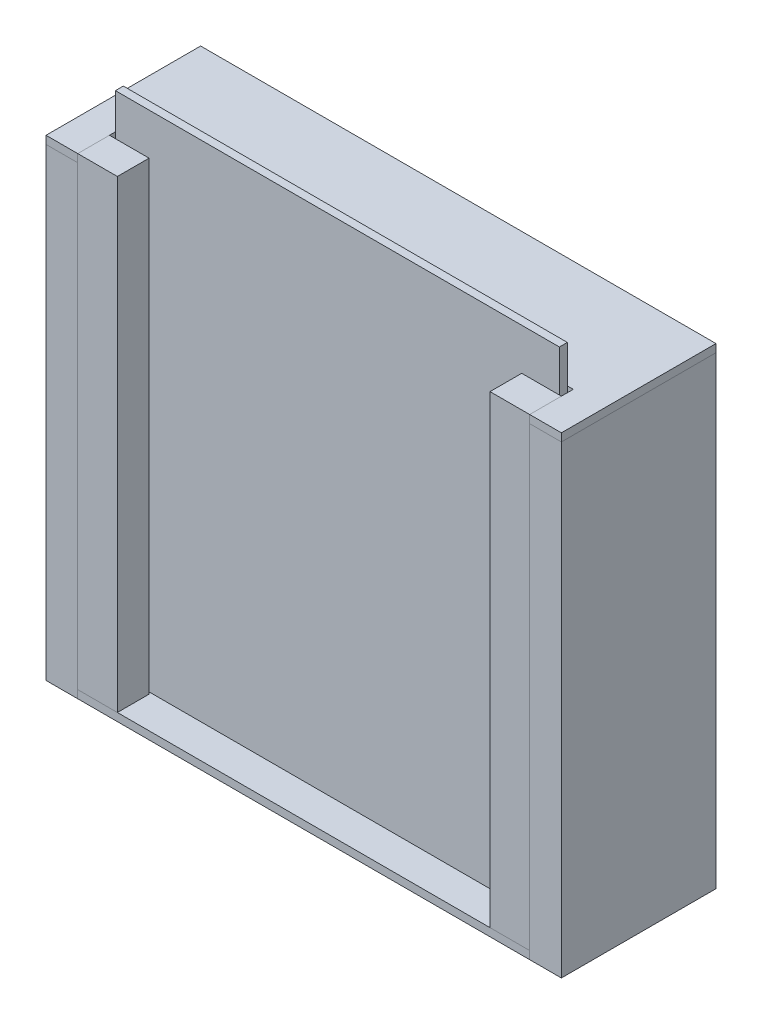
SolidWorks part; units mm, degrees
note: The reader was unsure of these and kept them because the rebuilt part matched: shared geometry of "스케치8<3>".
other "카메라1mm문"
other "카메라4mm 바깥레일2"
other "카메라4mm 바깥레일1"
other "카메라4mm 안쪽레일2"
other "카메라4mm 안쪽레일1"
other "카메라1mm천장"
other "카메라4mm벽2"
other "카메라4mm벽1"
other "바닥 1mm"
other "바닥1mm"
ref_plane "정면" through (0, 0, 0) normal (0, 0, 1) x (1, 0, 0)
ref_plane "윗면" through (0, 0, 0) normal (0, 1, 0) x (1, 0, 0)
ref_plane "우측면" through (0, 0, 0) normal (1, 0, 0) x (0, 0, -1)
sketch "스케치6" plane through (0, 0, 0) normal (0, 0, 1) x (1, 0, 0)
  line L1 (-32.5, 121.5) -> (-28.5, 121.5)
  line L2 (-32.5, 121.5) -> (-32.5, 180.05)
  line L3 (-32.5, 180.05) -> (-28.5, 180.05)
  line L4 (-28.5, 121.5) -> (-28.5, 180.05)
  line L5 (0, 181.05) -> (0, 118.3412) construction
  line L6 (-32.5, 181.05) -> (32.5, 181.05) construction
  line L7 (32.5, 121.5) -> (28.5, 121.5)
  line L8 (28.5, 121.5) -> (28.5, 180.05)
  line L9 (32.5, 180.05) -> (28.5, 180.05)
  line L10 (32.5, 121.5) -> (32.5, 180.05)
  dimension "D1" = 58.55
  dimension "D2" = 4
extrude "보스-돌출8" add sketch "스케치6" along normal blind 19.5
sketch "스케치7" plane through (0, 180.05, 0) normal (0, 1, 0) x (1, 0, 0)
  line L0 (-32.5, 0) -> (-32.5, -19.5)
  line L1 (-32.5, -19.5) -> (-28.5, -19.5)
  line L2 (-28.5, -19.5) -> (-28.5, -14)
  line L3 (-28.5, -19.5) -> (-28.5, 0) construction
  line L4 (-28.5, -14) -> (28.5, -14)
  line L5 (28.5, -19.5) -> (28.5, 0) construction
  line L6 (28.5, -14) -> (28.5, -19.5)
  line L7 (32.5, -19.5) -> (28.5, -19.5) construction
  line L8 (28.5, -19.5) -> (32.5, -19.5)
  line L9 (32.5, -19.5) -> (32.5, 0)
  line L10 (32.5, 0) -> (-32.5, 0)
  dimension "D1" = 5.5
extrude "보스-돌출9" add sketch "스케치7" along normal blind 1 separate body
sketch "스케치8" plane through (0, 121.5, 0) normal (0, -1, 0) x (1, 0, 0)
  line L0 (-28.5, 19.5) -> (-28.5, 0) construction
  line L1 (-28.5, 19.5) -> (-23.5, 19.5)
  line L2 (-28.5, 19.5) -> (-28.5, 15.5)
  line L3 (-28.5, 15.5) -> (-23.5, 15.5)
  line L4 (-23.5, 19.5) -> (-23.5, 15.5)
  line L5 (-28.5, 14) -> (-23.5, 14)
  line L6 (-28.5, 14) -> (-28.5, 10)
  line L7 (-28.5, 10) -> (-23.5, 10)
  line L8 (-23.5, 14) -> (-23.5, 10)
  line L9 (0, 14) -> (0, 16.8267) construction
  line L10 (-28.5, 14) -> (28.5, 14) construction
  line L11 (23.5, 14) -> (23.5, 10)
  line L12 (28.5, 10) -> (23.5, 10)
  line L13 (28.5, 14) -> (28.5, 10)
  line L14 (28.5, 14) -> (23.5, 14)
  line L15 (23.5, 19.5) -> (23.5, 15.5)
  line L16 (28.5, 15.5) -> (23.5, 15.5)
  line L17 (28.5, 19.5) -> (28.5, 15.5)
  line L18 (28.5, 19.5) -> (23.5, 19.5)
  line M2 (-28.5, 0) -> (-28.5, 19.5)
  dimension "D1" = 4
  dimension "D2" = 5
  dimension "D3" = 4
  dimension "D4" = 1.5
extrude "보스-돌출10" add sketch "스케치8" against normal up to surface (58.55 mm away) separate body contours L8 L5 L7 M2 | L13 L14 L11 L12 up to face at (0, 180.05, 13.25)
extrude "보스-돌출11" add sketch "스케치8<3>" against normal up to surface (59.55 mm away) separate body contours L4 L1 L3 M2 | L17 L18 L15 L16 up to face at (0, 181.05, 13.25)
sketch "스케치8<3>" plane through (0, 121.5, 0) normal (0, -1, 0) x (1, 0, 0) same geometry as "스케치8"
sketch "스케치9" plane through (0, 181.05, 0) normal (0, 1, 0) x (1, 0, 0)
  line L0 (-28.5, -15.5) -> (-23.5, -15.5) construction
  line L1 (-28, -14.25) -> (28, -14.25)
  line L2 (-28, -14.25) -> (-28, -15.25)
  line L3 (-28, -15.25) -> (28, -15.25)
  line L4 (28, -14.25) -> (28, -15.25)
  line L5 (-28.5, -19.5) -> (-28.5, -14) construction
  line L6 (28.5, -14) -> (28.5, -19.5) construction
  dimension "D1" = 1
  dimension "D2" = 0.25
  dimension "D3" = 0.5
  dimension "D4" = 0.5
extrude "보스-돌출12" add sketch "스케치9" against normal up to surface (59.55 mm away) separate body up to face at (-30.5, 121.5, 9.75)
sketch "스케치10" plane through (0, 181.05, 0) normal (0, 1, 0) x (1, 0, 0)
  line L4 (-28, -14.25) -> (-28, -15.25)
  line L5 (-28, -15.25) -> (28, -15.25)
  line L6 (28, -15.25) -> (28, -14.25)
  line L7 (28, -14.25) -> (-28, -14.25)
  line L8 (-28, -14.25) -> (-28, -15.25)
  line L9 (-28, -15.25) -> (28, -15.25)
  line L10 (28, -15.25) -> (28, -14.25)
  line L11 (28, -14.25) -> (-28, -14.25)
  dimension "D1" = 0
extrude "보스-돌출13" add sketch "스케치10" along normal blind 5
sketch "스케치11" plane through (0, 121.5, 0) normal (0, -1, 0) x (1, 0, 0)
  line L4 (-23.5, 15.5) -> (-23.5, 19.5)
  line L5 (-23.5, 19.5) -> (-28.5, 19.5)
  line L6 (-28.5, 19.5) -> (-28.5, 15.5)
  line L7 (-28.5, 15.5) -> (-23.5, 15.5)
  line L8 (-23.5, 15.5) -> (-23.5, 19.5)
  line L9 (-23.5, 19.5) -> (-28.5, 19.5)
  line L10 (-28.5, 19.5) -> (-28.5, 15.5)
  line L11 (-28.5, 15.5) -> (-23.5, 15.5)
  line L12 (-23.5, 10) -> (-23.5, 14)
  line L13 (-23.5, 14) -> (-28.5, 14)
  line L14 (-28.5, 14) -> (-28.5, 10)
  line L15 (-28.5, 10) -> (-23.5, 10)
  line L16 (-23.5, 10) -> (-23.5, 14)
  line L17 (-23.5, 14) -> (-28.5, 14)
  line L18 (-28.5, 14) -> (-28.5, 10)
  line L19 (-28.5, 10) -> (-23.5, 10)
  line L20 (28.5, 10) -> (28.5, 14)
  line L21 (28.5, 14) -> (23.5, 14)
  line L22 (23.5, 14) -> (23.5, 10)
  line L23 (23.5, 10) -> (28.5, 10)
  line L24 (28.5, 10) -> (28.5, 14)
  line L25 (28.5, 14) -> (23.5, 14)
  line L26 (23.5, 14) -> (23.5, 10)
  line L27 (23.5, 10) -> (28.5, 10)
  line L28 (28.5, 15.5) -> (28.5, 19.5)
  line L29 (28.5, 19.5) -> (23.5, 19.5)
  line L30 (23.5, 19.5) -> (23.5, 15.5)
  line L31 (23.5, 15.5) -> (28.5, 15.5)
  line L32 (28.5, 15.5) -> (28.5, 19.5)
  line L33 (28.5, 19.5) -> (23.5, 19.5)
  line L34 (23.5, 19.5) -> (23.5, 15.5)
  line L35 (23.5, 15.5) -> (28.5, 15.5)
  dimension "D1" = 0
  dimension "D2" = 0
  dimension "D3" = 0
  dimension "D4" = 0
extrude "컷-돌출5" cut sketch "스케치11" against normal blind 1
sketch "스케치12" plane through (0, 121.5, 0) normal (0, -1, 0) x (1, 0, 0)
  line L1 (-28.5, 19.5) -> (28.5, 19.5)
  line L2 (-28.5, 19.5) -> (-28.5, 10)
  line L3 (-28.5, 10) -> (28.5, 10)
  line L4 (28.5, 19.5) -> (28.5, 10)
extrude "보스-돌출14" add sketch "스케치12" against normal blind 1 separate body
sketch "스케치13" plane through (0, 121.5, 0) normal (0, -1, 0) x (1, 0, 0)
  line L4 (-28, 15.25) -> (-28, 14.25)
  line L5 (-28, 14.25) -> (28, 14.25)
  line L6 (28, 14.25) -> (28, 15.25)
  line L7 (28, 15.25) -> (-28, 15.25)
  line L8 (-28, 15.25) -> (-28, 14.25)
  line L9 (-28, 14.25) -> (28, 14.25)
  line L10 (28, 14.25) -> (28, 15.25)
  line L11 (28, 15.25) -> (-28, 15.25)
  dimension "D1" = 0
extrude "컷-돌출6" cut sketch "스케치13" against normal blind 1
sketch "스케치14" plane through (0, 121.5, 0) normal (0, -1, 0) x (1, 0, 0)
  line L1 (-28.5, 19.5) -> (28.5, 19.5)
  line L2 (-28.5, 19.5) -> (-28.5, 10)
  line L3 (-28.5, 10) -> (28.5, 10)
  line L4 (28.5, 19.5) -> (28.5, 10)
extrude "보스-돌출15" add sketch "스케치14" against normal blind 1 separate body
delete or keep bodies "바디-삭제/보존 1" type delete bodies bodies 131
other "바디 저장1"
